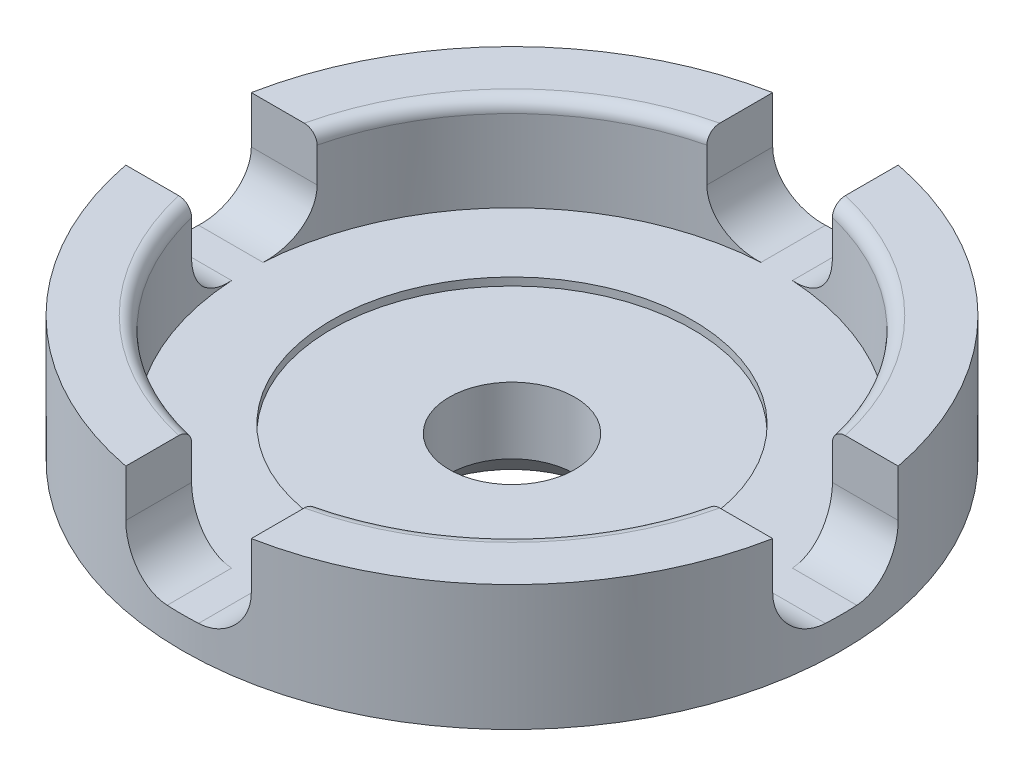
SolidWorks part; units mm, degrees
ref_plane "Front plane" through (0, 0, 0) normal (0, 0, 1) x (1, 0, 0)
ref_plane "Top plane" through (0, 0, 0) normal (0, 1, 0) x (1, 0, 0)
ref_plane "Right plane" through (0, 0, 0) normal (1, 0, 0) x (0, 0, -1)
ref_axis "Axis X" through (0, 0, 0) along (1, 0, 0)
ref_axis "Axis Y" through (0, 0, 0) along (0, 1, 0)
ref_axis "Axis Z" through (0, 0, 0) along (0, 0, 1)
sketch "Sketch1" plane through (0, 0, 0) normal (0, 1, 0) x (1, 0, 0)
  circle A0 centre (0, 0) radius 10.5
  dimension "D1" = 21
extrude "Extrude1" add sketch "Sketch1" along normal blind 1
sketch "Sketch6" plane through (0, 1, 0) normal (0, 1, 0) x (1, 0, 0)
  line L0 (-2, 10.3078) -> (-2, 8.2099)
  line L1 (2, 10.3078) -> (2, 8.2099)
  line L2 (0, 10) -> (0, 0) construction
  line L3 (10.3078, 2) -> (8.2099, 2)
  line L4 (10.3078, -2) -> (8.2099, -2)
  line L5 (2, -10.3078) -> (2, -8.2099)
  line L6 (-2, -10.3078) -> (-2, -8.2099)
  line L7 (-10.3078, -2) -> (-8.2099, -2)
  line L8 (-10.3078, 2) -> (-8.2099, 2)
  arc A0 (-2, 8.2099) -> (-8.2099, 2) centre (0, 0) ccw
  arc A1 (-2, 10.3078) -> (-10.3078, 2) centre (0, 0) ccw
  circle A2 centre (0, 0) radius 10.5 construction
  arc A3 (8.2099, 2) -> (2, 8.2099) centre (0, 0) ccw
  arc A4 (10.3078, 2) -> (2, 10.3078) centre (0, 0) ccw
  arc A5 (-8.2099, -2) -> (-2, -8.2099) centre (0, 0) ccw
  arc A6 (-10.3078, -2) -> (-2, -10.3078) centre (0, 0) ccw
  arc A7 (2, -8.2099) -> (8.2099, -2) centre (0, 0) ccw
  arc A8 (2, -10.3078) -> (10.3078, -2) centre (0, 0) ccw
  point P11 (2, 9.2588)
  point P27 (0, 0)
  dimension "D1" = 16.9
  dimension "D2" = 4
  dimension "D3" = 4
extrude "Extrude6" add sketch "Sketch6" along normal blind 3
sketch "Sketch9" plane through (0, 1, 0) normal (0, 1, 0) x (1, 0, 0)
  circle A0 centre (0, 0) radius 5.75
  dimension "D1" = 11.5
extrude "Extrude9" cut sketch "Sketch9" against normal blind 0.25
sketch "Sketch7" plane through (0, 0, 0) normal (0, -1, 0) x (1, 0, 0)
  circle A0 centre (0, 0) radius 4.9
  dimension "D1" = 9.8
extrude "Extrude7" add sketch "Sketch7" along normal blind 2.3667
sketch "Sketch8" plane through (0, -2.3667, 0) normal (0, -1, 0) x (1, 0, 0)
  circle A0 centre (0, 0) radius 2
  dimension "D1" = 4
extrude "Extrude8" cut sketch "Sketch8" against normal through all
fillet "Fillet2" radius 0.4 5 edges at (0, -2.3667, -4.9) (-5.9751, 4, -5.9751) (-5.9751, 4, 5.9751) (5.9751, 4, 5.9751) (5.9751, 4, -5.9751)
chamfer "Chamfer2" distance 1 angle 45 1 edges at (0, -2.3667, -2)
fillet "Fillet3" radius 1.5 8 edges at (9.2588, 1, 2) (9.2588, 1, -2) (2, 1, -9.2588) (-2, 1, -9.2588) (-2, 1, 9.2588) (2, 1, 9.2588) (-9.2588, 1, 2) (-9.2588, 1, -2)
equation "\"motor_D\"= 30'Motor diameter"
equation "\"motor_H\"= 13'Motor heigh"
equation "\"motor_d1\"= 25.4558'Seating diameter of screws on the fixed part of the motor"
equation "\"motor_s1\"= 2'Screws diameter on the fixed part of motor"
equation "\"motor_d2\"= 0'Seating diameter of screws on the moving part of the motor (if this parameter is not determine, write 0)"
equation "\"motor_a2\"= 10'Seating parameter in rectangle of screws on the moving part of the motor"
equation "\"motor_b2\"= 22'Seating parameter in rectangle of screws on the moving part of the motor"
equation "\"motor_s2\"= 2'Screws diameter on the moving part of motor"
equation "\"motor_cmd\"= 12'Central magnet mount diameter"
equation "\"motor_cmh\"= 1.4'Central magnet mount heigh (if not write 0)"
equation "\"motor_Dc\"= 5'Central hole diameter of motor"
equation "\"motor_whR\"= 10'Distance from center of motor to wires"
equation "\"bearing_d1\"= 6'Bearing inner diameter"
equation "\"bearing_d2\"= 17'Bearing external diameter"
equation "\"bearing h\"= 6'Bearing heigh"
equation "\"pin_d\"= 2'Pin diameter"
equation "\"pin_h\"= 12'Pin heigh"
equation "\"magnet_d1\"= 5'Magnet inner diameter"
equation "\"magnet_d2\"= 9.5'Magnet external diameter"
equation "\"magnet_h\"= 3'Magnet heigh"
equation "\"print_offset\"= 0.2'Offset for printing holes"
equation "\"ft_sensor_d1\"= 9.8"
equation "\"ft_sensor_d2\"= 24.9"
equation "\"ft_sensor_d3\"= 22.6'Inner diameter of "
equation "\"ft_sensor_h\"= 7.1"
equation "\"ft_sensor_whD\" = 5"
equation "\"D1@Sketch1\"=\"bearing_d2\"+4"
equation "\"D1@Sketch6\"=\"bearing_d2\"-\"print_offset\"*0.5"
equation "\"D1@Extrude6\"=\"bearing h\"/2"
equation "\"D1@Sketch7\"=\"ft_sensor_d1\""
equation "\"D1@Extrude7\"=\"ft_sensor_h\"/3"
equation "\"D1@Sketch9\"=(\"bearing_d1\"+\"bearing_d2\")/2"
